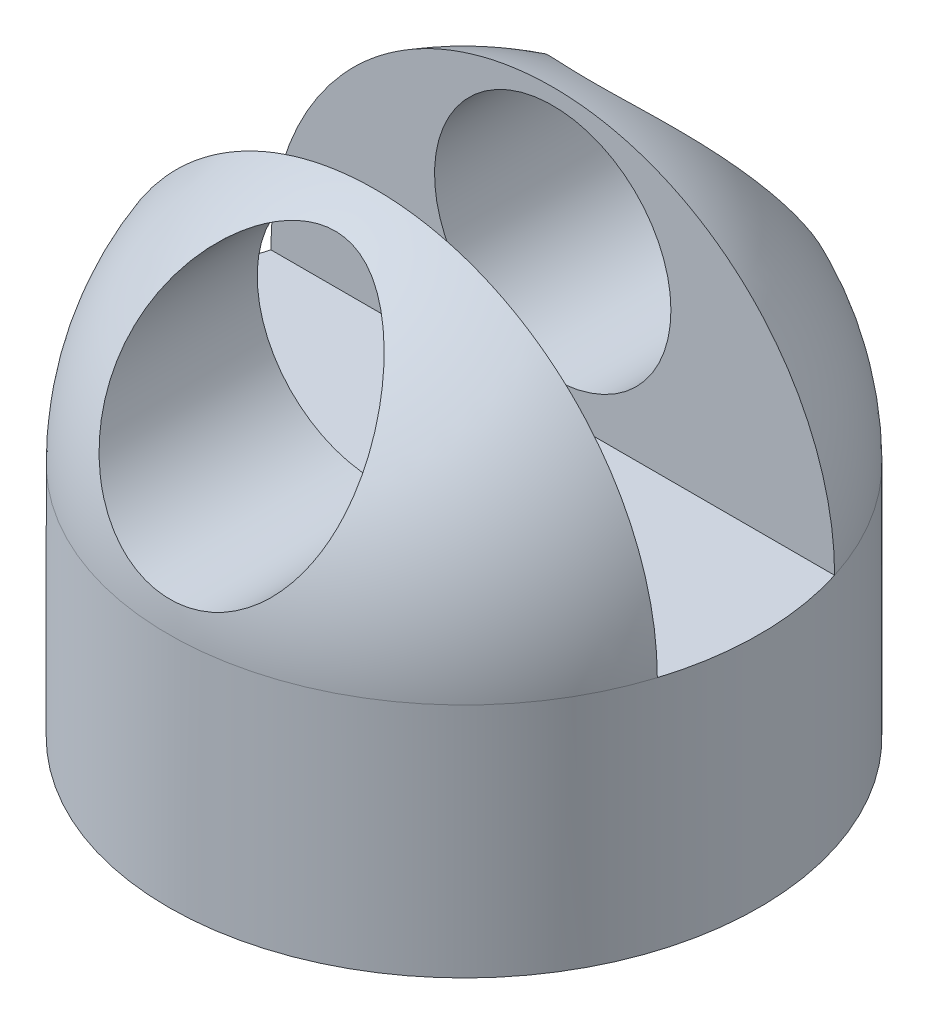
SolidWorks part; units mm, degrees
ref_plane "Front Plane" through (0, 0, 0) normal (0, 0, 1) x (1, 0, 0)
ref_plane "Top Plane" through (0, 0, 0) normal (0, 1, 0) x (1, 0, 0)
ref_plane "Right Plane" through (0, 0, 0) normal (1, 0, 0) x (0, 0, -1)
sketch "Sketch1" plane through (0, 0, 0) normal (0, 1, 0) x (1, 0, 0)
  circle A0 centre (0, 0) radius 25
  dimension "D1" = 50
extrude "Boss-Extrude1" add sketch "Sketch1" along normal blind 20
sketch "Sketch4" plane through (0, 0, 0) normal (0, 0, 1) x (1, 0, 0)
  line L0 (25, 20) -> (-25, 20) construction
  line L1 (0, 45) -> (0, 20)
  line L2 (0, 20) -> (25, 20)
  arc A0 (0, 45) -> (25, 20) centre (0, 20) cw
revolve "Revolve1" add sketch "Sketch4" angle 360 about L1
sketch "Sketch5" plane through (0, 0, 0) normal (1, 0, 0) x (0, 0, -1)
  line L0 (-25, 20) -> (25, 20) construction
  line L1 (0, 20) -> (7.5, 20)
  line L2 (0, 20) -> (0, 45.6269)
  line L3 (0, 45.6269) -> (7.5, 45.6269)
  line L4 (7.5, 20) -> (7.5, 45.6269)
  dimension "D1" = 7.5
extrude "Cut-Extrude1" cut sketch "Sketch5" against normal blind 25 and the other way blind 25
mirror "Mirror1" about plane through (0, 0, 0) normal (0, 0, 1) of "Cut-Extrude1"
sketch "Sketch6" plane through (0, 0, 0) normal (0, 0, 1) x (1, 0, 0)
  line L0 (25, 0) -> (25, 20) construction
  circle A0 centre (0, 32.5) radius 10
  dimension "D2" = 20
  dimension "D1" = 32.5
  dimension "D3" = 25
extrude "Cut-Extrude2" cut sketch "Sketch6" against normal blind 25 and the other way blind 25
